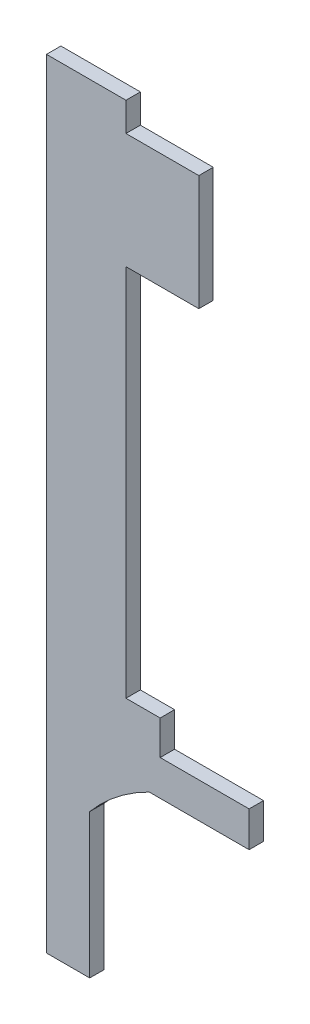
SolidWorks part; units mm, degrees
material "Balsa"
ref_plane "Plan de face" through (0, 0, 0) normal (0, 0, 1) x (1, 0, 0)
ref_plane "Plan de dessus" through (0, 0, 0) normal (0, 1, 0) x (1, 0, 0)
ref_plane "Plan de droite" through (0, 0, 0) normal (1, 0, 0) x (0, 0, -1)
sketch "Esquisse1" plane through (0, 0, 0) normal (0, 0, 1) x (1, 0, 0)
  line L0 (70.2972, 66.1864) -> (70.2972, 78.4512)
  line L1 (0, 270) -> (27.5725, 270)
  line L2 (70.2972, 78.4512) -> (39.4393, 78.4512)
  line L3 (15, 50) -> (15, 0)
  line L4 (0, 270) -> (0, 0)
  line L5 (15, 0) -> (0, 0)
  line L6 (27.5725, 270) -> (27.5725, 260)
  line L7 (35.67, 66.1864) -> (70.2972, 66.1864)
  line L8 (27.5725, 220) -> (52.855, 220)
  line L9 (52.855, 220) -> (52.855, 260)
  line L10 (27.5725, 260) -> (52.855, 260)
  line L11 (27.5725, 220) -> (27.5725, 90.334)
  line L12 (27.5725, 90.334) -> (39.4393, 90.334)
  line L13 (39.4393, 90.334) -> (39.4393, 78.4512)
  arc A0 (15, 50) -> (35.67, 66.1864) centre (63.603, 9.2251) cw
  dimension "D1" = 270
  dimension "D2" = 10
  dimension "D3" = 15
  dimension "D4" = 50
  dimension "D5" = 40
extrude "Boss.-Extru.1" add sketch "Esquisse1" along normal blind 5
